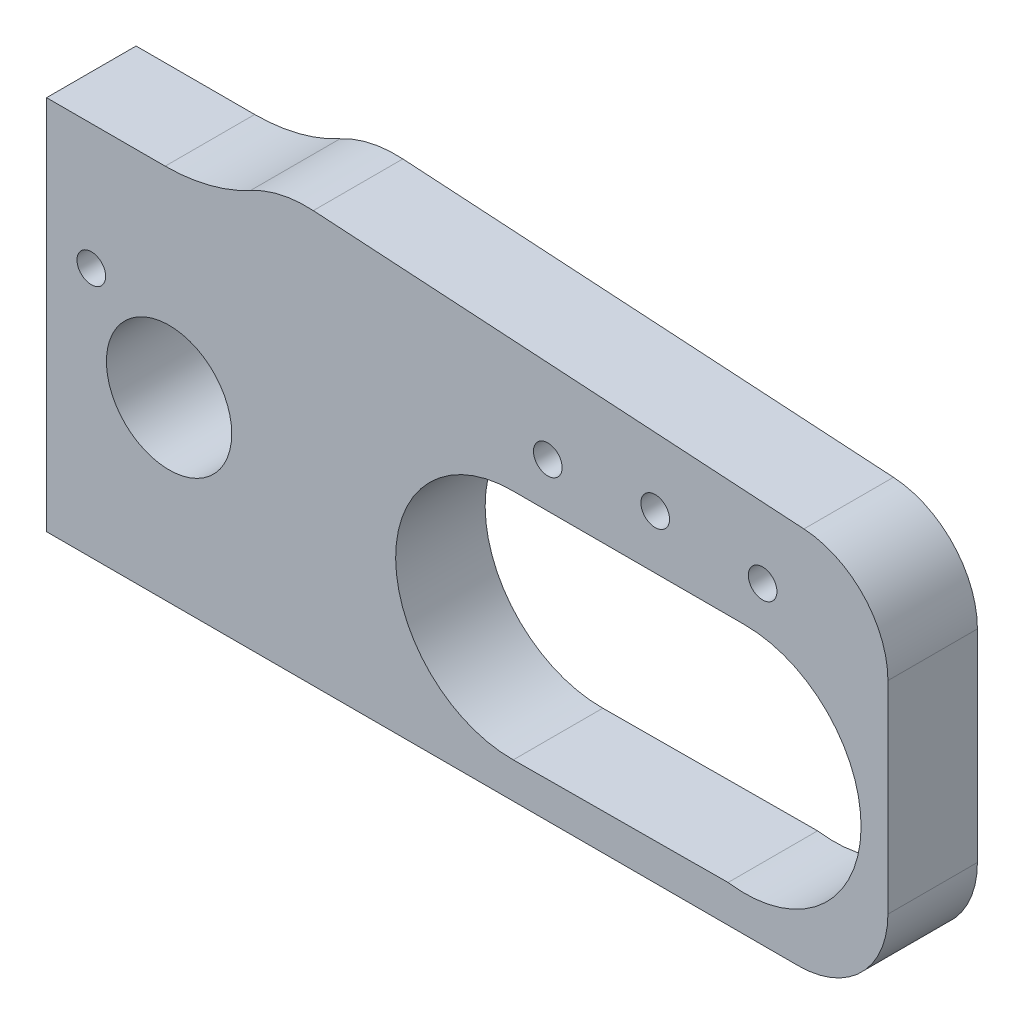
SolidWorks part; units mm, degrees
ref_plane "Front Plane" through (0, 0, 0) normal (1, 0, 0) x (0, 1, 0)
ref_plane "Top Plane" through (0, 0, 0) normal (0, 0, 1) x (0, 1, 0)
ref_plane "Right Plane" through (0, 0, 0) normal (0, 1, 0) x (-1, 0, 0)
sketch "Sketch1" plane through (0, 0, 0) normal (0, 0, 1) x (0, 1, 0)
  line L0 (12.9142, -18.3709) -> (14.6113, 9.0364)
  line L1 (7.9237, -23.0618) -> (-3.3763, -23.0618)
  line L4 (-8.3763, 23.9382) -> (12.6237, 23.9382)
  line L5 (12.6237, 23.9382) -> (12.6237, 17.3122)
  line L7 (-6.3763, -2.0618) -> (-6.2989, -16.0618)
  line L8 (6.6237, -15.0618) -> (6.6237, -2.0618)
  line L10 (-8.3763, 23.9382) -> (-8.3763, -18.0618)
  arc A2 (14.6113, 9.0364) -> (13.8358, 12.54) centre (8.1237, 9.4382) ccw
  arc A3 (12.6237, 17.3122) -> (13.8358, 12.54) centre (22.6237, 17.3122) ccw
  arc A4 (-8.3763, -18.0618) -> (-3.3763, -23.0618) centre (-3.3763, -18.0618) ccw
  arc A5 (7.9237, -23.0618) -> (12.9142, -18.3709) centre (7.9237, -18.0618) ccw
  circle A8 centre (5.6237, 21.4382) radius 0.8
  circle A9 centre (9.1237, -4.0618) radius 0.8
  circle A10 centre (9.6237, -10.0618) radius 0.8
  circle A11 centre (9.1237, -16.0618) radius 0.8
  arc A12 (6.6237, -2.0618) -> (-6.3759, -2.1337) centre (0.1237, -2.0618) ccw
  arc A13 (-6.3096, -14.1329) -> (6.6237, -15.0618) centre (0.1237, -15.0618) ccw
  circle A16 centre (8.1237, 9.4382) radius 5.1
  circle A18 centre (8.1237, 9.4382) radius 5.1
  circle A23 centre (1.537, 17.0949) radius 3.5
  dimension "D8" = 2.5
  dimension "D9" = 1.6
  dimension "D10" = 1.6
  dimension "D11" = 7
  dimension "D1" = 21
  dimension "D2" = 42
  dimension "D3" = 27.4598
  dimension "D4" = 11.3
  dimension "D5" = 2.5
  dimension "D6" = 2.5
  dimension "D7" = 3
extrude "Boss-Extrude1" add sketch "Sketch1" along normal blind 5 contours L1 A5 L0 A2 A3 L5 L4 L10 A4 A13 L7 A12 L8 A11 A10 A9 A8 region at (21.3237, 10.9899, 0)
sketch "Sketch2" plane through (-23.9382, 0, 0) normal (-1, 0, 0) x (0, -1, 0)
  line L0 (-12.6237, 2.5) -> (-9.6237, 2.5) construction
  line L1 (-12.6237, 5) -> (-12.6237, 0) construction
  line L2 (8.3763, 5) -> (8.3763, 0) construction
  circle A0 centre (-9.6237, 2.5) radius 1.25
  circle A1 centre (2.8763, 2.5) radius 1.25
  dimension "D2" = 5.5
  dimension "D3" = 2.5
  dimension "D4" = 2.5
  dimension "D1" = 3
  dimension "D5" = 0
extrude "Cut-Extrude1" cut sketch "Sketch2" against normal blind 4
sketch "Sketch21" plane through (0, 0, 5) normal (0, 0, 1) x (1, 0, 0)
  circle A0 centre (-9.4382, 8.1237) radius 5.1
extrude "Boss-Extrude2" add sketch "Sketch21" against normal blind 1
